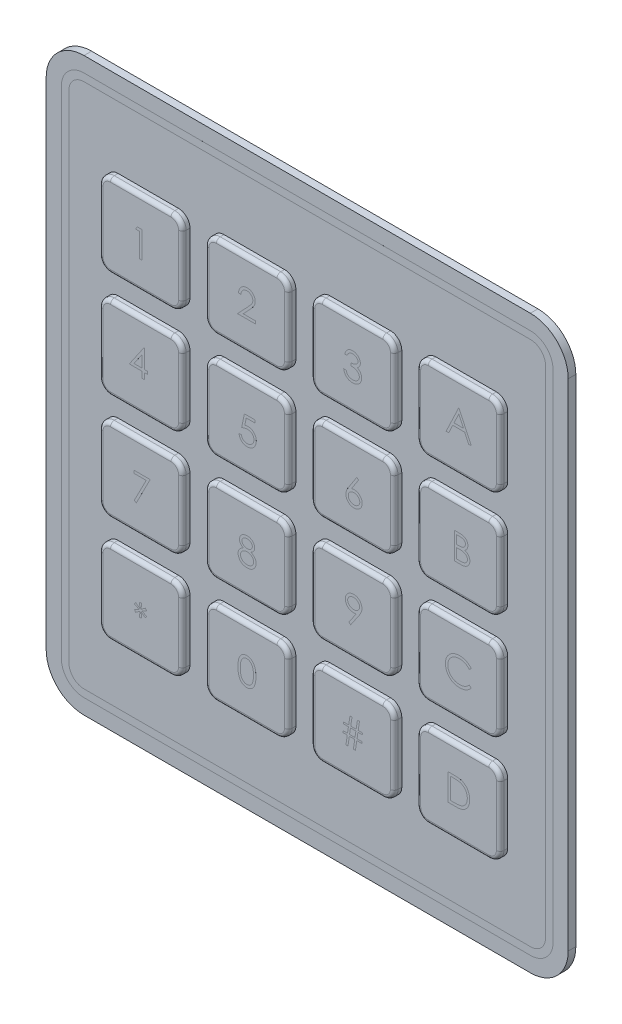
SolidWorks part; units mm, degrees
ref_plane "Alzado" through (0, 0, 0) normal (0, 0, 1) x (1, 0, 0)
ref_plane "Planta" through (0, 0, 0) normal (0, 1, 0) x (1, 0, 0)
ref_plane "Vista lateral" through (0, 0, 0) normal (1, 0, 0) x (0, 0, -1)
sketch "Croquis1" plane through (0, 0, 0) normal (0, 0, 1) x (1, 0, 0)
  line L1 (-29.5, -37.75) -> (29.5, -37.75)
  line L2 (-34.5, -32.75) -> (-34.5, 32.75)
  line L3 (-29.5, 37.75) -> (29.5, 37.75)
  line L4 (34.5, -32.75) -> (34.5, 32.75)
  line L5 (-34.5, -37.75) -> (34.5, 37.75) construction
  line L6 (-34.5, 37.75) -> (34.5, -37.75) construction
  arc A0 (-29.5, 37.75) -> (-34.5, 32.75) centre (-29.5, 32.75) ccw
  arc A1 (34.5, 32.75) -> (29.5, 37.75) centre (29.5, 32.75) ccw
  arc A2 (29.5, -37.75) -> (34.5, -32.75) centre (29.5, -32.75) ccw
  arc A3 (-29.5, -37.75) -> (-34.5, -32.75) centre (-29.5, -32.75) cw
  point P0 (0, 0)
  dimension "D3" = 5
  dimension "D4" = 5
  dimension "D5" = 5
  dimension "D1" = 75.5
  dimension "D2" = 69
extrude "Saliente-Extruir1" add sketch "Croquis1" along normal blind 1
sketch "Croquis2" plane through (0, 0, 1) normal (0, 0, 1) x (1, 0, 0)
  line L0 (-34.5, 0) -> (0, 0) construction
  line L1 (-25, 15.5) -> (-17, 15.5)
  line L2 (-26.5, 17) -> (-26.5, 25)
  line L3 (-25, 26.5) -> (-17, 26.5)
  line L4 (-15.5, 17) -> (-15.5, 25)
  line L5 (-26.5, 15.5) -> (-15.5, 26.5) construction
  line L6 (-26.5, 26.5) -> (-15.5, 15.5) construction
  line L7 (-34.5, 32.75) -> (-34.5, -32.75) construction
  line L8 (0, 0) -> (0, 37.75) construction
  line L9 (29.5, 37.75) -> (-29.5, 37.75) construction
  line L10 (-14, 0) -> (-14, 37.75) construction
  line L11 (-3, 15.5) -> (-11, 15.5)
  line L12 (-12.5, 17) -> (-12.5, 25)
  line L13 (-3, 26.5) -> (-11, 26.5)
  line L14 (-1.5, 17) -> (-1.5, 25)
  line L15 (-14, 14) -> (0, 14) construction
  line L16 (-12.5, 11) -> (-12.5, 3)
  line L17 (-3, 1.5) -> (-11, 1.5)
  line L18 (-1.5, 11) -> (-1.5, 3)
  line L19 (-3, 12.5) -> (-11, 12.5)
  line L20 (-25, 12.5) -> (-17, 12.5)
  line L21 (-15.5, 11) -> (-15.5, 3)
  line L22 (-26.5, 11) -> (-26.5, 3)
  line L23 (-25, 1.5) -> (-17, 1.5)
  line L24 (26.5, 26.5) -> (15.5, 15.5) construction
  line L25 (26.5, 15.5) -> (15.5, 26.5) construction
  line L26 (25, 1.5) -> (17, 1.5)
  line L27 (26.5, 11) -> (26.5, 3)
  line L28 (15.5, 11) -> (15.5, 3)
  line L29 (25, 12.5) -> (17, 12.5)
  line L30 (3, 12.5) -> (11, 12.5)
  line L31 (1.5, 11) -> (1.5, 3)
  line L32 (3, 1.5) -> (11, 1.5)
  line L33 (12.5, 11) -> (12.5, 3)
  line L34 (1.5, 17) -> (1.5, 25)
  line L35 (3, 26.5) -> (11, 26.5)
  line L36 (12.5, 17) -> (12.5, 25)
  line L37 (3, 15.5) -> (11, 15.5)
  line L38 (15.5, 17) -> (15.5, 25)
  line L39 (25, 26.5) -> (17, 26.5)
  line L40 (26.5, 17) -> (26.5, 25)
  line L41 (25, 15.5) -> (17, 15.5)
  line L42 (26.5, -15.5) -> (15.5, -26.5) construction
  line L43 (26.5, -26.5) -> (15.5, -15.5) construction
  line L44 (-14, -14) -> (0, -14) construction
  line L45 (-26.5, -26.5) -> (-15.5, -15.5) construction
  line L46 (-26.5, -15.5) -> (-15.5, -26.5) construction
  line L47 (25, -15.5) -> (17, -15.5)
  line L48 (26.5, -17) -> (26.5, -25)
  line L49 (25, -26.5) -> (17, -26.5)
  line L50 (15.5, -17) -> (15.5, -25)
  line L51 (3, -15.5) -> (11, -15.5)
  line L52 (12.5, -17) -> (12.5, -25)
  line L53 (3, -26.5) -> (11, -26.5)
  line L54 (1.5, -17) -> (1.5, -25)
  line L55 (12.5, -11) -> (12.5, -3)
  line L56 (3, -1.5) -> (11, -1.5)
  line L57 (1.5, -11) -> (1.5, -3)
  line L58 (3, -12.5) -> (11, -12.5)
  line L59 (25, -12.5) -> (17, -12.5)
  line L60 (15.5, -11) -> (15.5, -3)
  line L61 (26.5, -11) -> (26.5, -3)
  line L62 (25, -1.5) -> (17, -1.5)
  line L63 (-25, -1.5) -> (-17, -1.5)
  line L64 (-26.5, -11) -> (-26.5, -3)
  line L65 (-15.5, -11) -> (-15.5, -3)
  line L66 (-25, -12.5) -> (-17, -12.5)
  line L67 (-3, -12.5) -> (-11, -12.5)
  line L69 (-1.5, -11) -> (-1.5, -3)
  line L70 (-3, -1.5) -> (-11, -1.5)
  line L71 (-12.5, -11) -> (-12.5, -3)
  line L72 (-1.5, -17) -> (-1.5, -25)
  line L73 (-3, -26.5) -> (-11, -26.5)
  line L74 (-12.5, -17) -> (-12.5, -25)
  line L75 (-3, -15.5) -> (-11, -15.5)
  line L76 (-15.5, -17) -> (-15.5, -25)
  line L77 (-25, -26.5) -> (-17, -26.5)
  line L78 (-26.5, -17) -> (-26.5, -25)
  line L79 (-25, -15.5) -> (-17, -15.5)
  arc A0 (-17, 15.5) -> (-15.5, 17) centre (-17, 17) ccw
  arc A1 (-26.5, 25) -> (-25, 26.5) centre (-25, 25) cw
  arc A2 (-25, 15.5) -> (-26.5, 17) centre (-25, 17) cw
  arc A3 (-17, 26.5) -> (-15.5, 25) centre (-17, 25) cw
  arc A4 (-3, 15.5) -> (-1.5, 17) centre (-3, 17) ccw
  arc A5 (-11, 15.5) -> (-12.5, 17) centre (-11, 17) cw
  arc A6 (-11, 26.5) -> (-12.5, 25) centre (-11, 25) ccw
  arc A7 (-1.5, 25) -> (-3, 26.5) centre (-3, 25) ccw
  arc A8 (-11, 1.5) -> (-12.5, 3) centre (-11, 3) cw
  arc A9 (-1.5, 3) -> (-3, 1.5) centre (-3, 3) cw
  arc A10 (-3, 12.5) -> (-1.5, 11) centre (-3, 11) cw
  arc A11 (-11, 12.5) -> (-12.5, 11) centre (-11, 11) ccw
  arc A12 (-25, 12.5) -> (-26.5, 11) centre (-25, 11) ccw
  arc A13 (-17, 12.5) -> (-15.5, 11) centre (-17, 11) cw
  arc A14 (-17, 1.5) -> (-15.5, 3) centre (-17, 3) ccw
  arc A15 (-26.5, 3) -> (-25, 1.5) centre (-25, 3) ccw
  arc A16 (26.5, 3) -> (25, 1.5) centre (25, 3) cw
  arc A17 (17, 1.5) -> (15.5, 3) centre (17, 3) cw
  arc A18 (17, 12.5) -> (15.5, 11) centre (17, 11) ccw
  arc A19 (25, 12.5) -> (26.5, 11) centre (25, 11) cw
  arc A20 (11, 12.5) -> (12.5, 11) centre (11, 11) cw
  arc A21 (3, 12.5) -> (1.5, 11) centre (3, 11) ccw
  arc A22 (1.5, 3) -> (3, 1.5) centre (3, 3) ccw
  arc A23 (11, 1.5) -> (12.5, 3) centre (11, 3) ccw
  arc A24 (1.5, 25) -> (3, 26.5) centre (3, 25) cw
  arc A25 (11, 26.5) -> (12.5, 25) centre (11, 25) cw
  arc A26 (11, 15.5) -> (12.5, 17) centre (11, 17) ccw
  arc A27 (3, 15.5) -> (1.5, 17) centre (3, 17) cw
  arc A28 (17, 26.5) -> (15.5, 25) centre (17, 25) ccw
  arc A29 (25, 15.5) -> (26.5, 17) centre (25, 17) ccw
  arc A30 (26.5, 25) -> (25, 26.5) centre (25, 25) ccw
  arc A31 (17, 15.5) -> (15.5, 17) centre (17, 17) cw
  arc A32 (17, -15.5) -> (15.5, -17) centre (17, -17) ccw
  arc A33 (26.5, -25) -> (25, -26.5) centre (25, -25) cw
  arc A34 (25, -15.5) -> (26.5, -17) centre (25, -17) cw
  arc A35 (17, -26.5) -> (15.5, -25) centre (17, -25) cw
  arc A36 (3, -15.5) -> (1.5, -17) centre (3, -17) ccw
  arc A37 (11, -15.5) -> (12.5, -17) centre (11, -17) cw
  arc A38 (11, -26.5) -> (12.5, -25) centre (11, -25) ccw
  arc A39 (1.5, -25) -> (3, -26.5) centre (3, -25) ccw
  arc A40 (11, -1.5) -> (12.5, -3) centre (11, -3) cw
  arc A41 (1.5, -3) -> (3, -1.5) centre (3, -3) cw
  arc A42 (3, -12.5) -> (1.5, -11) centre (3, -11) cw
  arc A43 (11, -12.5) -> (12.5, -11) centre (11, -11) ccw
  arc A44 (25, -12.5) -> (26.5, -11) centre (25, -11) ccw
  arc A45 (17, -12.5) -> (15.5, -11) centre (17, -11) cw
  arc A46 (17, -1.5) -> (15.5, -3) centre (17, -3) ccw
  arc A47 (26.5, -3) -> (25, -1.5) centre (25, -3) ccw
  arc A48 (-26.5, -3) -> (-25, -1.5) centre (-25, -3) cw
  arc A49 (-17, -1.5) -> (-15.5, -3) centre (-17, -3) cw
  arc A50 (-17, -12.5) -> (-15.5, -11) centre (-17, -11) ccw
  arc A51 (-25, -12.5) -> (-26.5, -11) centre (-25, -11) cw
  arc A52 (-11, -12.5) -> (-12.5, -11) centre (-11, -11) cw
  arc A53 (-3, -12.5) -> (-1.5, -11) centre (-3, -11) ccw
  arc A54 (-1.5, -3) -> (-3, -1.5) centre (-3, -3) ccw
  arc A55 (-11, -1.5) -> (-12.5, -3) centre (-11, -3) ccw
  arc A56 (-1.5, -25) -> (-3, -26.5) centre (-3, -25) cw
  arc A57 (-11, -26.5) -> (-12.5, -25) centre (-11, -25) cw
  arc A58 (-11, -15.5) -> (-12.5, -17) centre (-11, -17) ccw
  arc A59 (-3, -15.5) -> (-1.5, -17) centre (-3, -17) cw
  arc A60 (-17, -26.5) -> (-15.5, -25) centre (-17, -25) ccw
  arc A61 (-25, -15.5) -> (-26.5, -17) centre (-25, -17) ccw
  arc A62 (-26.5, -25) -> (-25, -26.5) centre (-25, -25) ccw
  arc A63 (-17, -15.5) -> (-15.5, -17) centre (-17, -17) cw
  point P0 (-21, 21)
  point P117 (21, 21)
  point P226 (21, -21)
  point P227 (-21, -21)
  dimension "D2" = 11
  dimension "D3" = 1.5
  dimension "D1" = 11
  dimension "D4" = 21
  dimension "D5" = 21
  dimension "D6" = 1.5
  dimension "D7" = 1.5
extrude "Saliente-Extruir2" add sketch "Croquis2" along normal blind 1
fillet "Redondeo2" radius 0.5 128 edges at (-21, -26.5, 2) (-26.0607, -26.0607, 2) (-26.5, -21, 2) (-26.0607, -15.9393, 2) (-21, -15.5, 2) (-15.9393, -15.9393, 2) (-15.5, -21, 2) (-15.9393, -26.0607, 2) (-7, -26.5, 2) (-12.0607, -26.0607, 2) (-12.5, -21, 2) (-12.0607, -15.9393, 2) (-7, -15.5, 2) (-1.9393, -15.9393, 2) (-1.5, -21, 2) (-1.9393, -26.0607, 2) (7, -15.5, 2) (12.0607, -15.9393, 2) (12.5, -21, 2) (12.0607, -26.0607, 2) (7, -26.5, 2) (1.9393, -26.0607, 2) (1.5, -21, 2) (1.9393, -15.9393, 2) (21, -15.5, 2) (26.0607, -15.9393, 2) (26.5, -21, 2) (26.0607, -26.0607, 2) (21, -26.5, 2) (15.9393, -26.0607, 2) (15.5, -21, 2) (15.9393, -15.9393, 2) (21, -12.5, 2) (15.9393, -12.0607, 2) (15.5, -7, 2) (15.9393, -1.9393, 2) (21, -1.5, 2) (26.0607, -1.9393, 2) (26.5, -7, 2) (26.0607, -12.0607, 2) (12.5, -7, 2) (12.0607, -12.0607, 2) (7, -12.5, 2) (1.9393, -12.0607, 2) (1.5, -7, 2) (1.9393, -1.9393, 2) (7, -1.5, 2) (12.0607, -1.9393, 2) (-12.5, -7, 2) (-12.0607, -1.9393, 2) (-7, -1.5, 2) (-1.9393, -1.9393, 2) (-1.5, -7, 2) (-1.9393, -12.0607, 2) (-7, -12.5, 2) (-12.0607, -12.0607, 2) (-21, -1.5, 2) (-15.9393, -1.9393, 2) (-15.5, -7, 2) (-15.9393, -12.0607, 2) (-21, -12.5, 2) (-26.0607, -12.0607, 2) (-26.5, -7, 2) (-26.0607, -1.9393, 2) (-21, 12.5, 2) (-15.9393, 12.0607, 2) (-15.5, 7, 2) (-15.9393, 1.9393, 2) (-21, 1.5, 2) (-26.0607, 1.9393, 2) (-26.5, 7, 2) (-26.0607, 12.0607, 2) (-7, 12.5, 2) (-1.9393, 12.0607, 2) (-1.5, 7, 2) (-1.9393, 1.9393, 2) (-7, 1.5, 2) (-12.0607, 1.9393, 2) (-12.5, 7, 2) (-12.0607, 12.0607, 2) (12.5, 7, 2) (12.0607, 1.9393, 2) (7, 1.5, 2) (1.9393, 1.9393, 2) (1.5, 7, 2) (1.9393, 12.0607, 2) (7, 12.5, 2) (12.0607, 12.0607, 2) (21, 1.5, 2) (15.9393, 1.9393, 2) (15.5, 7, 2) (15.9393, 12.0607, 2) (21, 12.5, 2) (26.0607, 12.0607, 2) (26.5, 7, 2) (26.0607, 1.9393, 2) (21, 26.5, 2) (26.0607, 26.0607, 2) (26.5, 21, 2) (26.0607, 15.9393, 2) (21, 15.5, 2) (15.9393, 15.9393, 2) (15.5, 21, 2) (15.9393, 26.0607, 2) (7, 26.5, 2) (12.0607, 26.0607, 2) (12.5, 21, 2) (12.0607, 15.9393, 2) (7, 15.5, 2) (1.9393, 15.9393, 2) (1.5, 21, 2) (1.9393, 26.0607, 2) (-7, 15.5, 2) (-12.0607, 15.9393, 2) (-12.5, 21, 2) (-12.0607, 26.0607, 2) (-7, 26.5, 2) (-1.9393, 26.0607, 2) (-1.5, 21, 2) (-1.9393, 15.9393, 2) (-21, 15.5, 2) (-26.0607, 15.9393, 2) (-26.5, 21, 2) (-26.0607, 26.0607, 2) (-21, 26.5, 2) (-15.9393, 26.0607, 2) (-15.5, 21, 2) (-15.9393, 15.9393, 2)
sketch "Croquis3" plane through (0, 0, 1) normal (0, 0, 1) x (1, 0, 0)
  line L4 (29.5, 34.75) -> (-29.5, 34.75)
  line L5 (-31.5, 32.75) -> (-31.5, -32.75)
  line L6 (-29.5, -34.75) -> (29.5, -34.75)
  line L7 (31.5, -32.75) -> (31.5, 32.75)
  line L8 (-32.5, 32.75) -> (-32.5, -32.75)
  line L9 (-29.5, -35.75) -> (29.5, -35.75)
  line L10 (32.5, -32.75) -> (32.5, 32.75)
  line L11 (29.5, 35.75) -> (-29.5, 35.75)
  line L12 (-32.5, 32.75) -> (-32.5, -32.75)
  line L13 (-29.5, -35.75) -> (29.5, -35.75)
  line L14 (32.5, -32.75) -> (32.5, 32.75)
  line L15 (29.5, 35.75) -> (-29.5, 35.75)
  arc A4 (-29.5, 34.75) -> (-31.5, 32.75) centre (-29.5, 32.75) ccw
  arc A5 (-31.5, -32.75) -> (-29.5, -34.75) centre (-29.5, -32.75) ccw
  arc A6 (29.5, -34.75) -> (31.5, -32.75) centre (29.5, -32.75) ccw
  arc A7 (31.5, 32.75) -> (29.5, 34.75) centre (29.5, 32.75) ccw
  arc A8 (-29.5, 35.75) -> (-32.5, 32.75) centre (-29.5, 32.75) ccw
  arc A9 (-32.5, -32.75) -> (-29.5, -35.75) centre (-29.5, -32.75) ccw
  arc A10 (29.5, -35.75) -> (32.5, -32.75) centre (29.5, -32.75) ccw
  arc A11 (32.5, 32.75) -> (29.5, 35.75) centre (29.5, 32.75) ccw
  arc A12 (-29.5, 35.75) -> (-32.5, 32.75) centre (-29.5, 32.75) ccw
  arc A13 (-32.5, -32.75) -> (-29.5, -35.75) centre (-29.5, -32.75) ccw
  arc A14 (29.5, -35.75) -> (32.5, -32.75) centre (29.5, -32.75) ccw
  arc A15 (32.5, 32.75) -> (29.5, 35.75) centre (29.5, 32.75) ccw
  dimension "D1" = 2
  dimension "D2" = 1
extrude "Saliente-Extruir3" add sketch "Croquis3" along normal blind 0.0001
sketch "Croquis4" plane through (0, 0, 2) normal (0, 0, 1) x (1, 0, 0)
  line L0 (-26.5, 21) -> (26.5, 21) construction
  line L1 (-26.5, 25) -> (-26.5, 17) construction
  line L2 (26.5, 17) -> (26.5, 25) construction
  line L3 (-26.5, 7) -> (26.5, 7) construction
  line L4 (-26.5, 11) -> (-26.5, 3) construction
  line L5 (26.5, 11) -> (26.5, 3) construction
  line L6 (-26.5, -7) -> (26.5, -7) construction
  line L7 (-26.5, -3) -> (-26.5, -11) construction
  line L8 (26.5, -11) -> (26.5, -3) construction
  line L9 (-26.5, -21) -> (26.5, -21) construction
  line L10 (-26.5, -17) -> (-26.5, -25) construction
  line L11 (26.5, -25) -> (26.5, -17) construction
  line L12 (-21, 26.5) -> (-21, 15.5) construction
  line L13 (-17, 26.5) -> (-25, 26.5) construction
  line L14 (-25, 15.5) -> (-17, 15.5) construction
  line L15 (-21, 15.5) -> (-7, 26.5) construction
  line L16 (-3, 26.5) -> (-11, 26.5) construction
  line L17 (-7, 26.5) -> (-7, 15.5) construction
  line L18 (-11, 15.5) -> (-3, 15.5) construction
  line L19 (-7, 15.5) -> (7, 26.5) construction
  line L20 (11, 26.5) -> (3, 26.5) construction
  line L21 (7, 26.5) -> (7, 15.5) construction
  line L22 (3, 15.5) -> (11, 15.5) construction
  line L23 (7, 15.5) -> (21, 26.5) construction
  line L24 (25, 26.5) -> (17, 26.5) construction
  line L25 (21, 26.5) -> (21, 15.5) construction
  line L26 (17, 15.5) -> (25, 15.5) construction
  line L27 (21, 15.5) -> (21, -26.5) construction
  line L28 (17, -26.5) -> (25, -26.5) construction
  line L29 (21, -26.5) -> (7, 15.5) construction
  line L30 (7, 15.5) -> (7, -26.5) construction
  line L31 (3, -26.5) -> (11, -26.5) construction
  line L32 (7, -26.5) -> (-7, 15.5) construction
  line L33 (-7, 15.5) -> (-7, -26) construction
  line L34 (-11, -26) -> (-3, -26) construction
  line L35 (-7, -26) -> (-21, 16) construction
  line L36 (-25, 16) -> (-17, 16) construction
  line L37 (-21, 16) -> (-21, -26) construction
  line L38 (-25, -26) -> (-17, -26) construction
  text T0 "1"
  text T1 "2"
  text T2 "3"
  text T3 "4"
  text T4 "5"
  text T5 "6"
  text T6 "7"
  text T7 "8"
  text T8 "9"
  text T9 "*"
  text T10 "#"
  text T11 "A"
  text T12 "B"
  text T13 "C"
  text T14 "D"
  text T15 "0"
extrude "Saliente-Extruir4" add sketch "Croquis4" along normal blind 0.0001
sketch "Croquis5" plane through (0, 0, 0) normal (0, 0, -1) x (-1, 0, 0)
  line L1 (-10.75, -34.75) -> (10.75, -34.75)
  line L2 (-10.75, -34.75) -> (-10.75, -33.75)
  line L3 (-10.75, -33.75) -> (10.75, -33.75)
  line L4 (10.75, -34.75) -> (10.75, -33.75)
  line L5 (-10.75, -34.75) -> (10.75, -33.75) construction
  line L6 (-10.75, -33.75) -> (10.75, -34.75) construction
  line L7 (29.5, -37.75) -> (-29.5, -37.75) construction
  line L8 (0, 0) -> (0, -37.75) construction
  point P0 (0, -34.25)
  dimension "D1" = 21.5
  dimension "D2" = 1
  dimension "D4" = 3.5
extrude "Saliente-Extruir5" add sketch "Croquis5" along normal blind 1
